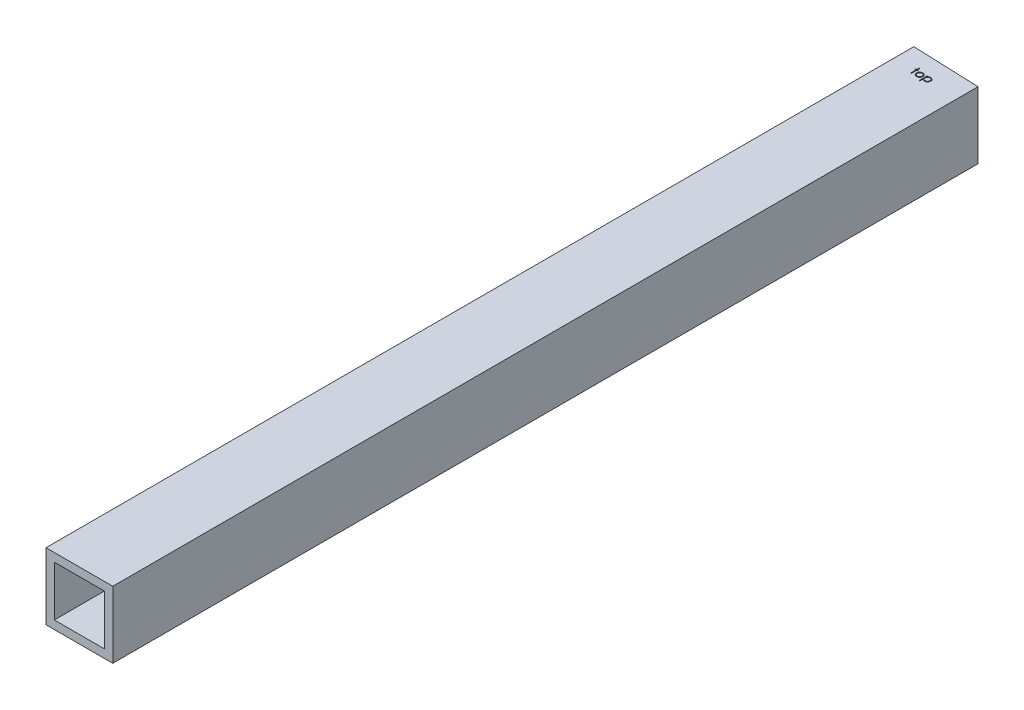
SolidWorks part; units mm, degrees
ref_plane "Front Plane" through (0, 0, 0) normal (0, 0, 1) x (1, 0, 0)
ref_plane "Top Plane" through (0, 0, 0) normal (0, 1, 0) x (1, 0, 0)
ref_plane "Right Plane" through (0, 0, 0) normal (1, 0, 0) x (0, 0, -1)
sketch "Sketch2" plane through (0, 0, 0) normal (0, 0, 1) x (1, 0, 0)
  line L1 (0, 0) -> (25.4, 0)
  line L2 (0, 0) -> (0, 25.4)
  line L3 (0, 25.4) -> (25.4, 25.4)
  line L4 (25.4, 0) -> (25.4, 25.4)
  line L5 (3.175, 22.225) -> (22.225, 22.225)
  line L6 (3.175, 22.225) -> (3.175, 3.175)
  line L7 (3.175, 3.175) -> (22.225, 3.175)
  line L8 (22.225, 22.225) -> (22.225, 3.175)
  dimension "D1" = 25.4
  dimension "D2" = 25.4
  dimension "D3" = 3.175
  dimension "D4" = 3.175
  dimension "D5" = 3.175
  dimension "D6" = 3.175
extrude "Boss-Extrude1" add sketch "Sketch2" along normal blind 330.2
sketch "Sketch3" plane through (0, 25.4, 0) normal (0, 1, 0) x (1, 0, 0)
  line L0 (0, 0) -> (25.4, -0.9775)
  line L1 (25.4, -330.2) -> (25.4, 0) construction
  line L2 (25.4, -0.9775) -> (25.4, 0)
  line L3 (25.4, 0) -> (0, 0)
  text T0 "top"
  dimension "D1" = 2.204
extrude "Cut-Extrude1" cut sketch "Sketch3" against normal through all
